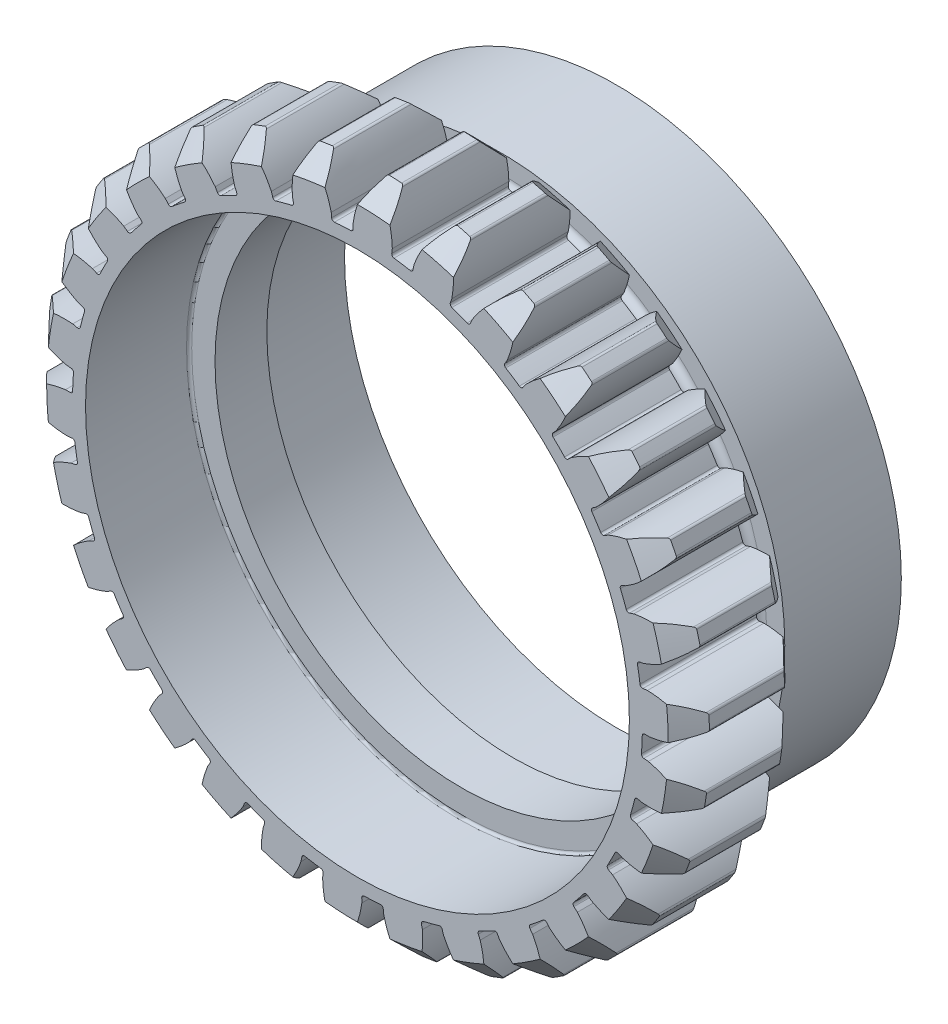
SolidWorks part; units mm, degrees
material "ABS"
ref_plane "Спереди" through (0, 0, 0) normal (0, 0, 1) x (1, 0, 0)
ref_plane "Сверху" through (0, 0, 0) normal (0, 1, 0) x (1, 0, 0)
ref_plane "Справа" through (0, 0, 0) normal (1, 0, 0) x (0, 0, -1)
sketch "Эскиз18" plane through (0, 0, 0) normal (1, 0, 0) x (0, 0, -1)
  line L0 (0, 0) -> (-5, 0) construction
  line L2 (-5, -10.5) -> (-1, -10.5)
  line L3 (-1, -10.5) -> (-1, -9.5)
  line L4 (-1, -9.5) -> (1, -9.5)
  line L5 (1, -9.5) -> (1, -10.5)
  line L6 (1, -10.5) -> (5, -10.5)
  line L7 (-5, -11) -> (-5, -10.5)
  line L13 (5, -11) -> (5, -10.5)
  line L14 (0, -9.5) -> (0, -18.1745) construction
  line L15 (5, -11) -> (0.5, -11)
  line L16 (0.5, -11) -> (0.5, -10)
  line L17 (0.5, -10) -> (-0.5, -10)
  line L18 (-0.5, -10) -> (-0.5, -11)
  line L19 (-0.5, -11) -> (-5, -11)
  point P11 (-5, 0)
  point P18 (-5, 0)
  point P19 (0, 0)
  dimension "D2" = 21
  dimension "D3" = 4
  dimension "D5" = 4
  dimension "D9" = 1
  dimension "D4" = 10
  dimension "D6" = 1
  dimension "D7" = 1
  dimension "D1" = 22
  dimension "D8" = 22
revolve "Повернуть1" add sketch "Эскиз18" angle 360 about L0
fillet "Скругление1" radius 0.3 2 edges at (-10, 0, -0.5) (-10, 0, 0.5)
fillet "Скругление2" radius 0.1 2 edges at (-10.5, 0, 1) (-10.5, 0, -1)
ref_plane "Плоскость1" through (0, 0, 2.75) normal (0, 0, 1) x (1, 0, 0)
sketch "Эскиз19" plane through (0, 0, 2.75) normal (0, 0, 1) x (1, 0, 0)
  line L0 (0, 0) -> (0, 12) construction
  line L1 (-1.239, 12) -> (1.239, 12) construction
  line L2 (0, 12) -> (3.8567, 10.5963) construction
  line L3 (0.3752, 12.7945) -> (5.6247, 9.7733) construction
  line L4 (0, 0) -> (-0.1681, 11.2751) construction
  line L5 (-0.1681, 11.2751) -> (-0.1639, 10.9988)
  line L6 (0, 0) -> (0.6699, 12.7825) construction
  line L7 (1.3457, 11.1957) -> (1.3127, 10.9214)
  circle A0 centre (0, 0) radius 11 construction
  arc A1 (1.3127, 10.9214) -> (-0.1639, 10.9988) centre (0, 0) ccw
  arc A2 (0.9643, 12.7636) -> (0.3752, 12.7945) centre (0, 0) ccw
  circle A3 centre (0, 0) radius 12 construction
  circle A4 centre (0, 0) radius 11.2763 construction
  spline S0 degree 2 poles (-0.1681, 11.2751) (-0.0597, 12.0915) (0.3752, 12.7945) knots 0 0 0 1 1 1
  spline S1 degree 2 poles (1.3457, 11.1957) (1.3233, 12.019) (0.9643, 12.7636) knots 0 0 0 1 1 1
  point P2 (-3.6603, 12)
  point P3 (1.2469, 11.9668)
  point P9 (0, 12)
  point P17 (-0.1681, 11.2751)
  dimension "D1" = 25.6
  dimension "D2" = 24
  dimension "D3" = 20
  dimension "D4" = 4.1042
  dimension "D5" = 6.0568
  dimension "D8" = 3
  dimension "D6" = 1.9526
  dimension "D7" = 4.1042
extrude "Бобышка-Вытянуть1" add sketch "Эскиз19" along normal mid plane 4.5
fillet "Скругление3" radius 0.1 4 edges at (-0.1639, 10.9988, 2.75) (1.3127, 10.9214, 2.75) (0.9643, 12.7636, 2.75) (0.3752, 12.7945, 2.75)
pattern_circular "Круговой массив1" count 30 over 360 about axis through (0, 0, 0) along (0, 0, -1) of "Бобышка-Вытянуть1", "Скругление3"
sketch "Эскиз21" plane through (0, 0, 0) normal (1, 0, 0) x (0, 0, -1)
  line L0 (-5, 0) -> (-5, 12.8) construction
  line L1 (-5, 0) -> (-0.5, 0) construction
  line L2 (-5, 0.3445) -> (-5, -0.1681) construction
  line L3 (-5, 12.8) -> (-0.5, 12.8) construction
  line L4 (-0.5, 12.8) -> (-0.5, 0) construction
  line L5 (-0.5, -10.3) -> (-0.5, 10.3) construction
  line L6 (1.1, 0) -> (5, 0) construction
  line L7 (-5, 12) -> (-0.5, 12) construction
  line L8 (-5, 12) -> (-5, 12.8)
  line L9 (-5, 12.8) -> (-4.2, 12.8)
  line L10 (-4.2, 12.8) -> (-5, 12)
  line L11 (-2.75, 12.8) -> (-2.75, 0) construction
  line L12 (-0.5, 12.8) -> (-1.3, 12.8)
  line L13 (-1.3, 12.8) -> (-0.5, 12)
  line L14 (-0.5, 12) -> (-0.5, 12.8)
  dimension "D1" = 12.8
  dimension "D2" = 12
revolve "Вырез-Повернуть1" cut sketch "Эскиз21" angle 360 about axis through (0, 0, 0) along (0, 0, -1)
equation "\"Модуль\"= 0.8мм"
equation "\"Число зубьев\"= 30"
equation "\"D1@Эскиз18\"= \"Модуль\" * (\"Число зубьев\" - 2.5)"
equation "\"D1@Эскиз19\"= \"Модуль\" * (\"Число зубьев\" + 2)"
equation "\"D2@Эскиз19\"= \"Модуль\" * \"Число зубьев\""
equation "\"D6@Эскиз19\"= \"D5@Эскиз19\" - \"D4@Эскиз19\""
equation "\"D7@Эскиз19\"= \"D4@Эскиз19\""
equation "\"D8@Эскиз19\"= 90 / \"Число зубьев\""
equation "\"D1@Круговой массив1\"= \"Число зубьев\""
equation "\"D1@Эскиз21\"= \"Модуль\" * (\"Число зубьев\" + 2) / 2"
equation "\"D2@Эскиз21\"=\"Модуль\" * \"Число зубьев\" / 2"
